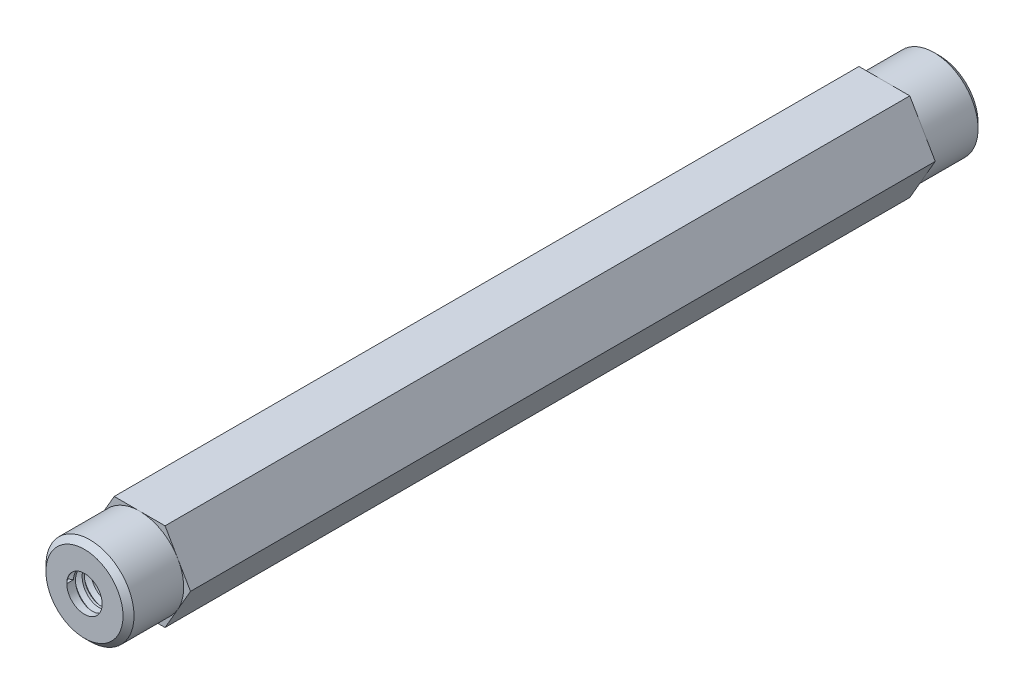
SolidWorks part; units mm, degrees
material "7075-T6 (SN)"
ref_plane "Alzado" through (0, 0, 0) normal (0, 0, 1) x (1, 0, 0)
ref_plane "Planta" through (0, 0, 0) normal (0, 1, 0) x (1, 0, 0)
ref_plane "Vista lateral" through (0, 0, 0) normal (1, 0, 0) x (0, 0, -1)
sketch "Croquis2" plane through (0, 0, 0) normal (0, 0, 1) x (1, 0, 0)
  line L1 (3.6662, -6.35) -> (7.3323, 0)
  line L2 (7.3323, 0) -> (3.6662, 6.35)
  line L3 (3.6662, 6.35) -> (-3.6662, 6.35)
  line L4 (-3.6662, 6.35) -> (-7.3323, 0)
  line L5 (-7.3323, 0) -> (-3.6662, -6.35)
  line L6 (-3.6662, -6.35) -> (3.6662, -6.35)
  circle A0 centre (0, 0) radius 6.35 construction
  dimension "D1" = 12.7
extrude "Extrusión Hex Profile" add sketch "Croquis2" along normal mid plane 123.2563
sketch "Croquis3" plane through (0, 0, 0) normal (0, 0, 1) x (1, 0, 0)
  circle A0 centre (0, 0) radius 2.5527
  dimension "D1" = 5.1054
extrude "Tap Hole 1" cut sketch "Croquis3" against normal blind 19.05 from surface starting at face at (0, 0, 61.6282)
extrude "Tap Hole 2" cut sketch "Croquis3<3>" along normal blind 19.05 from surface starting at face at (0, 0, -61.6282)
sketch "Croquis3<3>" plane through (0, 0, 0) normal (0, 0, 1) x (1, 0, 0) same geometry as "Croquis3"
sketch "Croquis7" plane through (0, 0, 0) normal (0, 0, 1) x (1, 0, 0)
  circle A0 centre (0, 0) radius 6.8707
  dimension "D1" = 13.7414
extrude "ThunderHex" [suppressed] cut sketch "Croquis7" against normal through all both and the other way through all flip side to cut
sketch "Croquis8" plane through (0, 0, 0) normal (0, 1, 0) x (1, 0, 0)
  line L0 (0, -61.6282) -> (-5.5562, -61.6282) construction
  line L1 (3.6662, -61.6282) -> (-3.6662, -61.6282) construction
  line L3 (0, -61.6282) -> (0, 0) construction
  line L4 (-5.5562, -61.6282) -> (-6.35, -60.8344)
  line L5 (-6.35, -60.8344) -> (-6.35, -60.0407)
  line L6 (-6.35, -60.0407) -> (-5.9055, -60.0407)
  line L7 (-5.9055, -60.0407) -> (-5.9055, -58.4532)
  line L8 (-5.9055, -58.4532) -> (-12.7, -58.4532)
  line L9 (-12.7, -58.4532) -> (-12.7, -61.6282)
  line L10 (-12.7, -61.6282) -> (-5.5562, -61.6282)
  line L11 (-3.6662, -61.6282) -> (-7.3323, -61.6282) construction
  dimension "D1" = 11.811
  dimension "D2" = 12.7
  dimension "D3" = 45
  dimension "D4" = 0.7937
  dimension "D6" = 0.7937
  dimension "D7" = 3.175
  dimension "D8" = 25.4
revolve "Retaining Ring 1" [suppressed] cut sketch "Croquis8" angle 360 about L3
sketch "Croquis9" plane through (0, 0, 0) normal (0, -1, 0) x (1, 0, 0)
  line L0 (0, -61.6282) -> (-5.5562, -61.6282) construction
  line L3 (0, -61.6282) -> (0, 0) construction
  line L4 (-5.5562, -61.6282) -> (-6.35, -60.8344)
  line L5 (-6.35, -60.8344) -> (-6.35, -60.0407)
  line L6 (-6.35, -60.0407) -> (-5.9055, -60.0407)
  line L7 (-5.9055, -60.0407) -> (-5.9055, -58.4532)
  line L8 (-5.9055, -58.4532) -> (-12.7, -58.4532)
  line L9 (-12.7, -58.4532) -> (-12.7, -61.6282)
  line L10 (-12.7, -61.6282) -> (-5.5562, -61.6282)
  line L12 (-3.6662, -61.6282) -> (3.6662, -61.6282) construction
  line L13 (-7.3323, -61.6282) -> (-3.6662, -61.6282) construction
  dimension "D1" = 11.811
  dimension "D2" = 12.7
  dimension "D3" = 45
  dimension "D4" = 0.7937
  dimension "D6" = 0.7937
  dimension "D7" = 3.175
  dimension "D8" = 25.4
revolve "Retaining Ring 2" [suppressed] cut sketch "Croquis9" angle 360 about L3
sketch "Croquis10" plane through (0, 0, 0) normal (0, 1, 0) x (1, 0, 0)
  line L0 (0, -61.6282) -> (0, 0) construction
  line L1 (3.6662, -61.6282) -> (-3.6662, -61.6282) construction
  line L2 (0, -61.6282) -> (-5.5562, -61.6282) construction
  line L3 (-3.6662, -61.6282) -> (-7.3323, -61.6282) construction
  line L4 (-5.5562, -61.6282) -> (-6.35, -60.8344)
  line L5 (-6.35, -60.8344) -> (-6.35, -53.678)
  line L6 (-6.35, -53.678) -> (-9.525, -53.678)
  line L7 (-9.525, -53.678) -> (-9.525, -61.6282)
  line L8 (-9.525, -61.6282) -> (-5.5562, -61.6282)
  dimension "D2" = 12.7
  dimension "D1" = 45
  dimension "D3" = 0.7937
  dimension "D4" = 7.9502
  dimension "D5" = 19.05
revolve "Round End 1" cut sketch "Croquis10" angle 360 about L0
sketch "Croquis12" plane through (0, 0, 0) normal (0, -1, 0) x (1, 0, 0)
  line L0 (0, -61.6282) -> (0, 0) construction
  line L2 (0, -61.6282) -> (-5.5562, -61.6282) construction
  line L4 (-5.5562, -61.6282) -> (-6.35, -60.8344)
  line L5 (-6.35, -60.8344) -> (-6.35, -53.678)
  line L6 (-6.35, -53.678) -> (-9.525, -53.678)
  line L7 (-9.525, -53.678) -> (-9.525, -61.6282)
  line L8 (-9.525, -61.6282) -> (-5.5562, -61.6282)
  line L9 (-3.6662, -61.6282) -> (3.6662, -61.6282) construction
  dimension "D1" = 45
  dimension "D3" = 0.7937
  dimension "D4" = 7.9502
  dimension "D2" = 12.7
  dimension "D5" = 19.05
revolve "Round End 2" cut sketch "Croquis12" angle 360 about L0
thread "Rosca1" pitch 1.27 method cut profile "Perfil de rosca1" start angle 0, offset 0, length 0, pitch 1.27, diameter 5.1054
ref_plane "Plano1" through (-2.5527, 0, 61.6282) normal (0, -1, 0) x (-1, 0, 0)
sketch "Perfil de rosca1" plane through (-2.5527, 0, 61.6282) normal (0, -1, 0) x (-1, 0, 0)
  line L0 (0, 0) -> (0, 1.27) construction
  line L1 (0, 0) -> (0.6874, 0.3969)
  line L2 (0.6874, 0.3969) -> (0.6874, 0.5556)
  line L3 (0.6874, 0.5556) -> (0, 0.9525)
  line L4 (0.6874, 0.4762) -> (0, 0.4762) construction
  line L11 (0, 0) -> (0, 0.9525)
  point P2 (0, 0)
  dimension "Pitch" = 1.27
  dimension "Profile_Angle" = 60
  dimension "Profile_Land" = 0.1588
  dimension "Profile_Height" = 0.6874
thread "Rosca2" pitch 1.27 method cut profile "Perfil de rosca2" start angle 0, offset 0, length 0, pitch 1.27, diameter 5.1054
ref_plane "Plano2" through (2.5527, 0, -61.6282) normal (0, -1, 0) x (1, 0, 0)
sketch "Perfil de rosca2" plane through (2.5527, 0, -61.6282) normal (0, -1, 0) x (1, 0, 0)
  line L0 (0, 0) -> (0, 1.27) construction
  line L1 (0, 0) -> (0.6874, 0.3969)
  line L2 (0.6874, 0.3969) -> (0.6874, 0.5556)
  line L3 (0.6874, 0.5556) -> (0, 0.9525)
  line L4 (0.6874, 0.4762) -> (0, 0.4762) construction
  line L11 (0, 0) -> (0, 0.9525)
  point P2 (0, 0)
  dimension "Pitch" = 1.27
  dimension "Profile_Angle" = 60
  dimension "Profile_Land" = 0.1588
  dimension "Profile_Height" = 0.6874
equation "\"HexOD\"= 0.5pulgadas"
equation "\"Largo\"= 4.85261024pulgadas"
equation "\"D1@Croquis2\"=\"HexOD\""
equation "\"D1@Extrusión Hex Profile\" = \"Largo\""
equation "\"TapHole\"= IIF ( \"HexOD\" = 0.5pulgadas , 0.2010pulgadas , 0.190pulgadas )"
equation "\"D1@Croquis3\"=\"TapHole\""
equation "\"ProTapHole\"= 0.75pulgadas"
equation "\"D1@Tap Hole 1\" = \"ProTapHole\""
equation "\"D1@Tap Hole 2\" = \"ProTapHole\""
equation "\"ThunderHex\"= IIF ( \"HexOD\" = 0.5pulgadas , 0.541pulgadas , 0.4035pulgadas )"
equation "\"D1@Croquis7\"=\"ThunderHex\""
equation "\"D2@Croquis8\"=\"HexOD\""
equation "\"D1@Croquis8\"=if(\"HexOD\"=0.5pulgadas, 0.465pulgadas, 0.35pulgadas )"
equation "\"D2@Croquis9\"=\"HexOD\""
equation "\"D1@Croquis9\"=if(\"HexOD\"=0.5pulgadas, 0.465pulgadas, 0.35pulgadas )"
equation "\"D8@Croquis8\"=\"HexOD\"*2"
equation "\"D8@Croquis9\"=\"HexOD\"*2"
equation "\"D5@Croquis10\"=\"HexOD\"*1.5"
equation "\"D5@Croquis12\"=\"HexOD\"*1.5"
equation "\"D4@Croquis10\"=if( \"D2@Croquis10\"=<0.375, 0.28, 0.313)"
equation "\"D4@Croquis12\"=if( \"D2@Croquis10\"=<0.375, 0.28, 0.313)"
